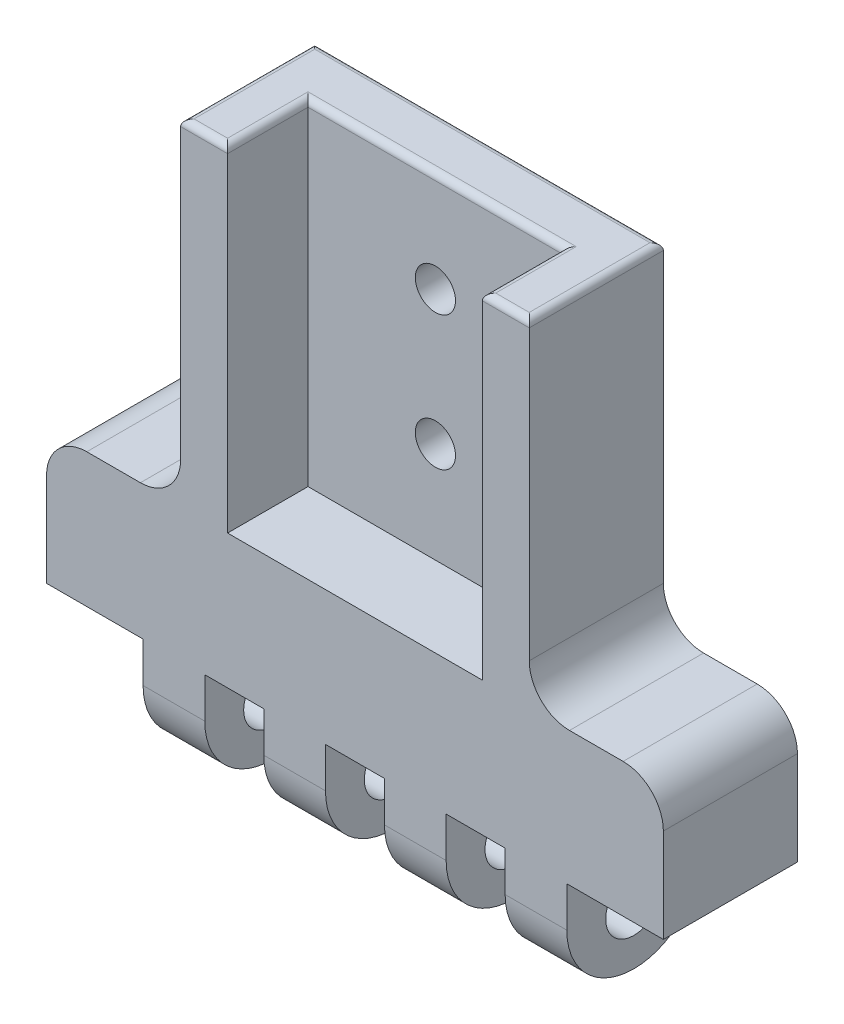
SolidWorks part; units mm, degrees
ref_plane "Front Plane" through (0, 0, 0) normal (0, 0, 1) x (1, 0, 0)
ref_plane "Top Plane" through (0, 0, 0) normal (0, 1, 0) x (1, 0, 0)
ref_plane "Right Plane" through (0, 0, 0) normal (1, 0, 0) x (0, 0, -1)
sketch "Sketch1" plane through (0, 0, 0) normal (0, 1, 0) x (1, 0, 0)
  line L1 (23, 5) -> (-23, 5)
  line L2 (23, 5) -> (23, -5)
  line L3 (23, -5) -> (-23, -5)
  line L4 (-23, 5) -> (-23, -5)
  line L5 (23, 5) -> (-23, -5) construction
  line L6 (23, -5) -> (-23, 5) construction
  point P0 (0, 0)
extrude "Boss-Extrude1" add sketch "Sketch1" along normal blind 10
sketch "Sketch2" plane through (0, 0, 0) normal (0, -1, 0) x (1, 0, 0)
  line L0 (23, -5) -> (-23, -5) construction
  line L1 (15.8, -5) -> (11.2, -5)
  line L2 (15.8, -5) -> (15.8, 5)
  line L3 (15.8, 5) -> (11.2, 5)
  line L4 (11.2, -5) -> (11.2, 5)
  line L5 (13.5, 5) -> (13.5, -5) construction
  line L6 (15.8, 0) -> (11.2, 0) construction
  line L7 (-23, 5) -> (23, 5) construction
  point P272 (13.5, 0)
  dimension "D2" = 4.6
extrude "Boss-Extrude2" add sketch "Sketch2" along normal blind 8
fillet "Fillet1" radius 5 2 edges at (13.5, -8, -5) (13.5, -8, 5)
pattern_linear "LPattern1" count 4 spacing 9 along (-1, 0, 0) of "Boss-Extrude2", "Fillet1"
sketch "Sketch4" plane through (15.8, 0, 0) normal (1, 0, 0) x (0, 0, -1)
  circle A0 centre (0, -3.74) radius 2.1
extrude "Cut-Extrude1" cut sketch "Sketch4" against normal through all
sketch "Sketch6" plane through (0, 0, 0) normal (0, 1, 0) x (1, 0, 0)
  line L1 (-13, -5) -> (13, -5)
  line L2 (-13, -5) -> (-13, 5)
  line L3 (-13, 5) -> (13, 5)
  line L4 (13, -5) -> (13, 5)
  line L5 (-13, -5) -> (13, 5) construction
  line L6 (-13, 5) -> (13, -5) construction
  point P0 (0, 0)
  dimension "D1" = 26
  dimension "D2" = 10
extrude "Boss-Extrude3" add sketch "Sketch6" along normal blind 35
ref_plane "Plane2" through (0, 35, 0) normal (0, 1, 0) x (1, 0, 0)
sketch "Sketch7" plane through (0, 35, 0) normal (0, 1, 0) x (1, 0, 0)
  line L0 (-13, -5) -> (13, -5) construction
  line L1 (-9.5, 1) -> (9.5, 1)
  line L2 (-9.5, 1) -> (-9.5, -5)
  line L3 (-9.5, -5) -> (9.5, -5)
  line L4 (9.5, 1) -> (9.5, -5)
  line L5 (-9.5, 1) -> (9.5, -5) construction
  line L6 (-9.5, -5) -> (9.5, 1) construction
  line L7 (13, -5) -> (13, 5) construction
  point P0 (0, -2)
  dimension "D1" = 19
  dimension "D2" = 6
  dimension "D3" = 13
extrude "Cut-Extrude2" cut sketch "Sketch7" against normal blind 25
sketch "Sketch8" plane through (0, 0, 0) normal (0, 0, 1) x (1, 0, 0)
  line L0 (-16.4869, 22.5) -> (18.6382, 22.5) construction
  line L1 (5.5, 35) -> (-5.5, 35) construction
  line L2 (9.5, 10) -> (9.5, 35) construction
  circle A0 centre (0, 27.5) radius 1.5
  circle A1 centre (0, 17.5) radius 1.5
  point P10 (0, 0)
  dimension "D1" = 3
  dimension "D2" = 10
  dimension "D3" = 5
  dimension "D4" = 12.5
  dimension "D5" = 9.5
extrude "Cut-Extrude3" cut sketch "Sketch8" against normal mid plane 25
fillet "Fillet2" radius 3 4 edges at (23, 10, 0) (13, 10, 0) (-23, 10, 0) (-13, 10, 0)
fillet "Fillet3" radius 0.5 8 edges at (11.25, 35, 5) (-11.25, 35, 5) (-9.5, 35, 2) (0, 35, -1) (9.5, 35, 2) (13, 35, 0) (0, 35, -5) (-13, 35, 0)
